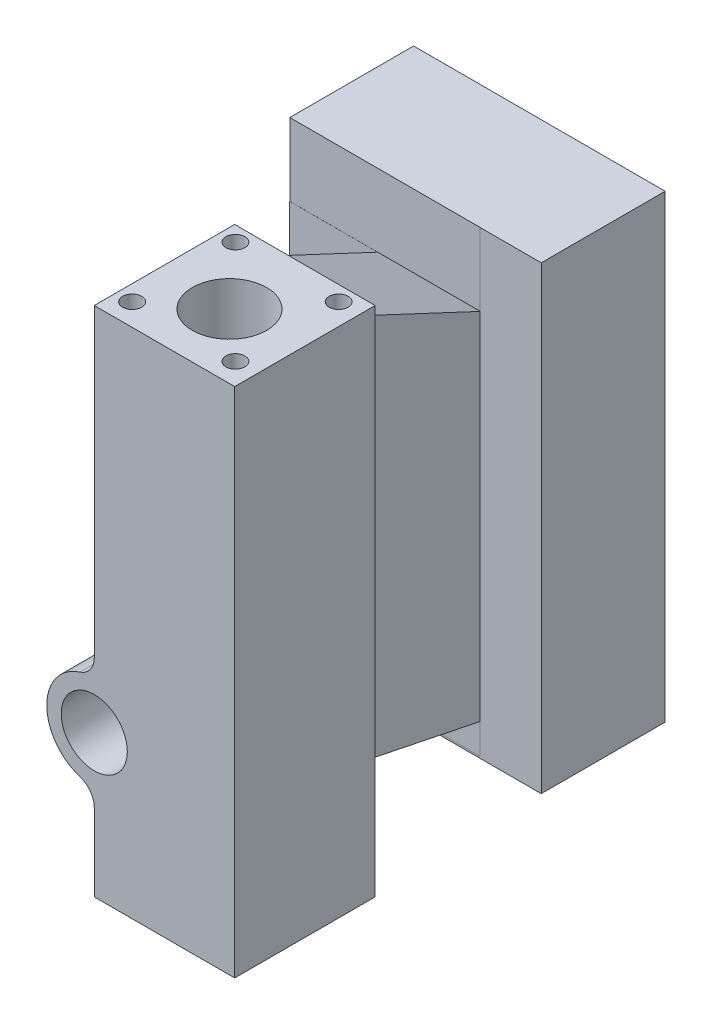
SolidWorks part; units mm, degrees
ref_plane "Front Plane" through (0, 0, 0) normal (0, 0, 1) x (1, 0, 0)
ref_plane "Top Plane" through (0, 0, 0) normal (0, 1, 0) x (1, 0, 0)
ref_plane "Right Plane" through (0, 0, 0) normal (1, 0, 0) x (0, 0, -1)
sketch "Sketch1" plane through (0, 0, 0) normal (0, 0, 1) x (1, 0, 0)
  line L1 (-22.1812, 49.3094) -> (11.8188, 49.3094)
  line L2 (-22.1812, 49.3094) -> (-22.1812, -74.6906)
  line L3 (-22.1812, -74.6906) -> (11.8188, -74.6906)
  line L4 (11.8188, 49.3094) -> (11.8188, -74.6906)
  dimension "D1" = 124
  dimension "D2" = 34
extrude "Boss-Extrude1" add sketch "Sketch1" along normal blind 34
sketch "Sketch2" plane through (0, 0, 34) normal (0, 0, 1) x (1, 0, 0)
  line L0 (-22.1812, 49.3094) -> (-22.1812, -74.6906) construction
  circle A0 centre (-22.1812, -40.2508) radius 11.504
extrude "Boss-Extrude2" add sketch "Sketch2" against normal blind 34
fillet "Fillet1" radius 5 2 edges at (-22.1812, -51.7548, 17) (-22.1812, -28.7468, 17)
sketch "Sketch3" plane through (0, -74.6906, 0) normal (0, -1, 0) x (1, 0, 0)
  circle A0 centre (-4.8936, 17.1062) radius 13.5862
extrude "Cut-Extrude1" cut sketch "Sketch3" against normal blind 50
sketch "Sketch4" plane through (0, 0, 34) normal (0, 0, 1) x (1, 0, 0)
  circle A0 centre (-22.1812, -40.2508) radius 8
  arc A1 (-25.6665, -29.2874) -> (-25.6665, -51.2142) centre (-22.1812, -40.2508) ccw construction
extrude "Cut-Extrude2" cut sketch "Sketch4" against normal blind 20
sketch "Sketch5" plane through (0, 0, 0) normal (0, 0, -1) x (-1, 0, 0)
  line L1 (-7.2618, 48.6909) -> (17.5691, 48.6909)
  line L2 (-7.2618, 48.6909) -> (-7.2618, -62.513)
  line L3 (-7.2618, -62.513) -> (17.5691, -62.513)
  line L4 (17.5691, 48.6909) -> (17.5691, -62.513)
extrude "Boss-Extrude3" add sketch "Sketch5" along normal blind 30
sketch "Sketch6" plane through (0, 0, -30) normal (0, 0, -1) x (-1, 0, 0)
  line L1 (-22.0319, 48.3699) -> (38.868, 48.3699)
  line L2 (-22.0319, 48.3699) -> (-22.0319, -62.9411)
  line L3 (-22.0319, -62.9411) -> (38.868, -62.9411)
  line L4 (38.868, 48.3699) -> (38.868, -62.9411)
extrude "Boss-Extrude4" add sketch "Sketch6" along normal blind 30
sketch "Sketch7" plane through (0, 49.3094, 0) normal (0, 1, 0) x (1, 0, 0)
  circle A0 centre (-5.0915, -18.3589) radius 8.9987
extrude "Cut-Extrude3" cut sketch "Sketch7" against normal blind 100
sketch "Sketch9" plane through (7.2618, 0, 0) normal (1, 0, 0) x (0, 0, -1)
  line L0 (-0.0119, 53.1584) -> (-0.0119, 44.8625)
  line L1 (-0.0119, 44.8625) -> (30.0187, 30.7835)
  line L2 (30.0187, 30.7835) -> (30.0187, 53.1584)
  line L3 (30.0187, 53.1584) -> (-0.0119, 53.1584)
  line L4 (-0.0119, -49.0284) -> (-0.0119, -66.3738)
  line L5 (-0.0119, -66.3738) -> (29.9948, -69.2814)
  line L6 (29.9948, -69.2814) -> (29.9948, -55.1732)
  line L7 (29.9948, -55.1732) -> (-0.0119, -49.0284)
extrude "Cut-Extrude5" cut sketch "Sketch9" against normal blind 100
sketch "Sketch10" plane through (-38.868, 0, 0) normal (-1, 0, 0) x (0, 0, 1)
  line L0 (-60, -62.9411) -> (-60, 48.3699) construction
  line L1 (-60, -62.9411) -> (-30, -62.9411) construction
  circle A0 centre (-45, -22.9411) radius 8.0865
  dimension "D1" = 15
  dimension "D2" = 40
extrude "Cut-Extrude6" cut sketch "Sketch10" against normal blind 10
sketch "Sketch11" plane through (0, 49.3094, 0) normal (0, 1, 0) x (1, 0, 0)
  circle A0 centre (6.6247, -28.639) radius 2.3015
extrude "Cut-Extrude7" cut sketch "Sketch11" against normal blind 10
pattern_linear "LPattern1" count 2 spacing 25 along (-1, 0, 0) count 2 spacing 25 along (0, 0, -1) of "Cut-Extrude7"
